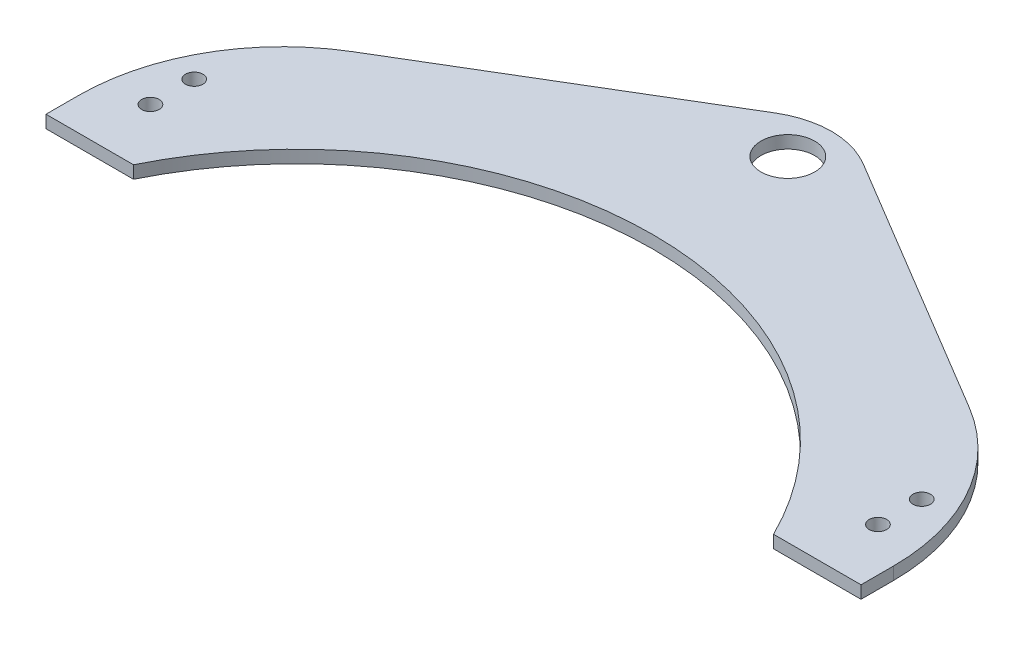
SolidWorks part; units mm, degrees
ref_plane "Front Plane" through (0, 0, 0) normal (0, 0, 1) x (1, 0, 0)
ref_plane "Top Plane" through (0, 0, 0) normal (0, 1, 0) x (1, 0, 0)
ref_plane "Right Plane" through (0, 0, 0) normal (1, 0, 0) x (0, 0, -1)
sketch "Sketch1" plane through (0, 0, 0) normal (0, 1, 0) x (1, 0, 0)
  line L0 (0, 0) -> (109.7, 0)
  line L1 (54.85, 0) -> (54.85, 39.9)
  line L2 (109.7, 0) -> (124.7, 0)
  line L3 (0, 0) -> (-15, 0)
  line L4 (124.7, 0) -> (124.7, 16.895)
  line L5 (-15, 0) -> (-15, 16.895)
  line L6 (54.85, 0) -> (54.85, 57.3)
  line L7 (54.85, 57.3) -> (54.85, 64.8)
  line L8 (54.85, 64.8) -> (54.7052, 64.8)
  line L9 (54.85, 64.8) -> (54.9948, 64.8)
  line L10 (62.4068, 62.6719) -> (117.4016, 29.7668)
  line L11 (47.2932, 62.6719) -> (-7.7016, 29.7668)
  line L12 (117.2, 0) -> (117.2, 10.4)
  line L13 (117.2, 10.4) -> (117.2, 17.9)
  line L14 (-7.5, 0) -> (-7.5, 10.4)
  line L15 (107.6704, 35.5893) -> (62.4068, 62.6719)
  line L16 (124.7, 5.5549) -> (124.7, 0)
  line L17 (47.2932, 62.6719) -> (2.0296, 35.5893)
  line L18 (-15, 5.5549) -> (-15, 0)
  line L19 (-7.5, 10.4) -> (-7.5, 17.9)
  arc A0 (0, 0) -> (109.7, 0) centre (54.85, -26.9726) cw
  circle A1 centre (54.85, 57.3) radius 4.6
  arc A2 (54.7052, 64.8) -> (62.4068, 62.6719) centre (54.7052, 49.8) cw
  arc A3 (54.9948, 64.8) -> (47.2932, 62.6719) centre (54.9948, 49.8) ccw
  arc A4 (-15, 16.895) -> (-7.7016, 29.7668) centre (0, 16.895) cw
  arc A5 (124.7, 16.895) -> (117.4016, 29.7668) centre (109.7, 16.895) ccw
  circle A6 centre (117.2, 17.9) radius 1.5
  circle A7 centre (117.2, 10.4) radius 1.5
  arc A10 (107.6704, 35.5893) -> (124.7, 5.5549) centre (89.7, 5.5549) cw
  arc A11 (2.0296, 35.5893) -> (-15, 5.5549) centre (20, 5.5549) ccw
  circle A13 centre (-7.5, 17.9) radius 1.5
  circle A14 centre (-7.5, 10.4) radius 1.5
  point P17 (58.85, 64.8)
  point P20 (50.85, 64.8)
  point P23 (-15, 25.4)
  point P26 (124.7, 25.4)
  point P41 (124.7, 25.4)
  point P44 (-15, 25.4)
  dimension "D8" = 7.5
  dimension "D11" = 15
  dimension "D12" = 15
  dimension "D15" = 10.4
  dimension "D16" = 35
  dimension "D17" = 7.5
  dimension "D1" = 109.7
  dimension "D2" = 39.9
  dimension "D3" = 15
  dimension "D4" = 15
  dimension "D5" = 25.4
  dimension "D6" = 25.4
  dimension "D7" = 57.3
  dimension "D9" = 4
  dimension "D10" = 4
  dimension "D13" = 10.4
  dimension "D14" = 7.5
extrude "Boss-Extrude2" add sketch "Sketch1" along normal blind 3.175 contours L11 A11 L5 L3 A13 A0 L6 A1 L7 L9 A3 | A10 L10 A2 L8 L7 A1 L6 A0 L2 A7 A6 L4 region at (20.0487, 0, -32.1504) region at (89.6513, 0, -32.1504)
sketch "Sketch2" plane through (0, 3.175, 0) normal (0, 1, 0) x (1, 0, 0)
  line L1 (-67.6712, -28.5428) -> (168.2941, -28.5428)
  line L2 (-67.6712, -28.5428) -> (-67.6712, 90.1788)
  line L3 (-67.6712, 90.1788) -> (168.2941, 90.1788)
  line L4 (168.2941, -28.5428) -> (168.2941, 90.1788)
extrude "Cut-Extrude1" cut sketch "Sketch2" against normal blind 1.016
